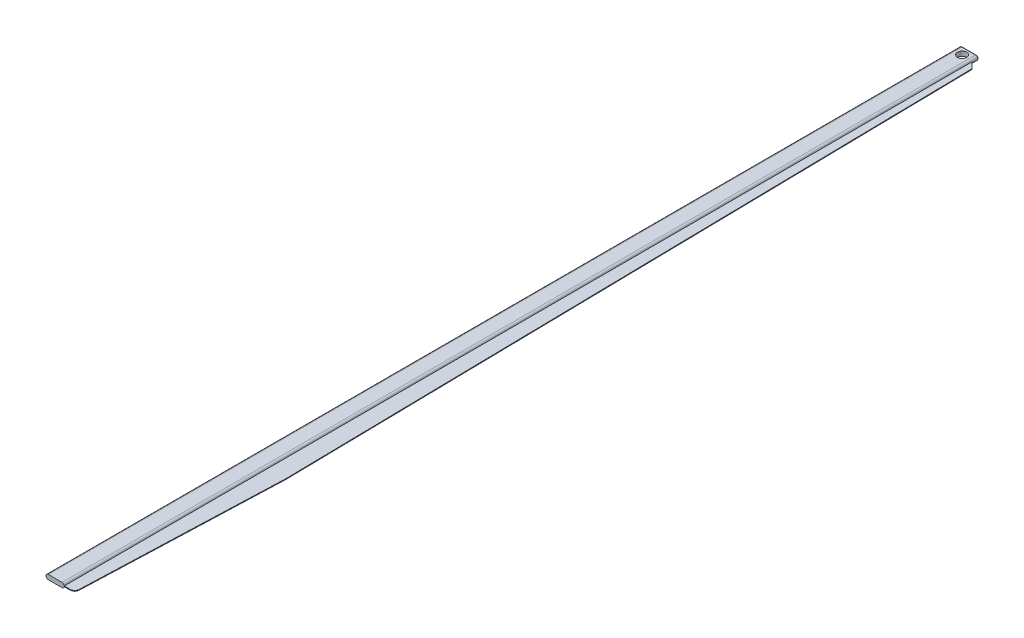
SolidWorks part; units mm, degrees
ref_plane "Front Plane" through (0, 0, 0) normal (0, 0, 1) x (1, 0, 0)
ref_plane "Top Plane" through (0, 0, 0) normal (0, 1, 0) x (1, 0, 0)
ref_plane "Right Plane" through (0, 0, 0) normal (1, 0, 0) x (0, 0, -1)
sketch "Sketch1" plane through (0, 0, 0) normal (0, 0, 1) x (1, 0, 0)
  line L0 (-375, 0) -> (375, 0) construction
  line L1 (-375, 125) -> (375, 125)
  line L2 (-375, -125) -> (375, -125)
  arc A0 (-375, 125) -> (-375, -125) centre (-375, 0) ccw
  arc A1 (375, -125) -> (375, 125) centre (375, 0) ccw
  point P3 (0, 0)
  point P8 (0, 0)
  dimension "D2" = 125
  dimension "D1" = 750
sketch "Sketch2" plane through (0, 0, 0) normal (0, 1, 0) x (1, 0, 0)
  line L0 (0, 0) -> (0, -50000)
  dimension "D1" = 50000
sweep "Sweep1" add profiles "Sketch1" path "Sketch2"
sketch "Sketch3" plane through (0, 0, 0) normal (0, 1, 0) x (1, 0, 0)
  line L0 (500, -366.0254) -> (500, -50000)
  line L1 (500, -50000) -> (500, 0) construction
  line L2 (375, -50000) -> (500, -50000) construction
  line L10 (500, -50000) -> (823.3419, -50000)
  line L14 (1474.7102, -38991.5397) -> (1073.1682, -49759.3163)
  line L15 (500, -366.0254) -> (823.3419, -689.3673)
  line L16 (823.3419, -689.3673) -> (1477.6678, -38733.4255)
  arc A8 (1477.6678, -38733.4255) -> (1474.7102, -38991.5397) centre (-3521.8169, -38805.2139) cw
  arc A9 (823.3419, -50000) -> (1073.1682, -49759.3163) centre (823.3419, -49750) ccw
  dimension "D1" = 5000
  dimension "D2" = 250
extrude "Boss-Extrude1" add sketch "Sketch3" along normal blind 20 and the other way blind 20 separate body
sketch "Sketch4" plane through (0, 125, 0) normal (0, 1, 0) x (1, 0, 0)
  line L0 (0, 0) -> (0, -400) construction
  line L1 (375, 0) -> (-375, 0) construction
  circle A0 centre (0, -400) radius 250
  dimension "D1" = 500
  dimension "D2" = 400
extrude "Cut-Extrude1" cut sketch "Sketch4" against normal through all
fillet "Fillet1" radius 50 4 edges at (0, 125, 0) (500, 0, 0) (0, -125, 0) (-500, 0, 0)
